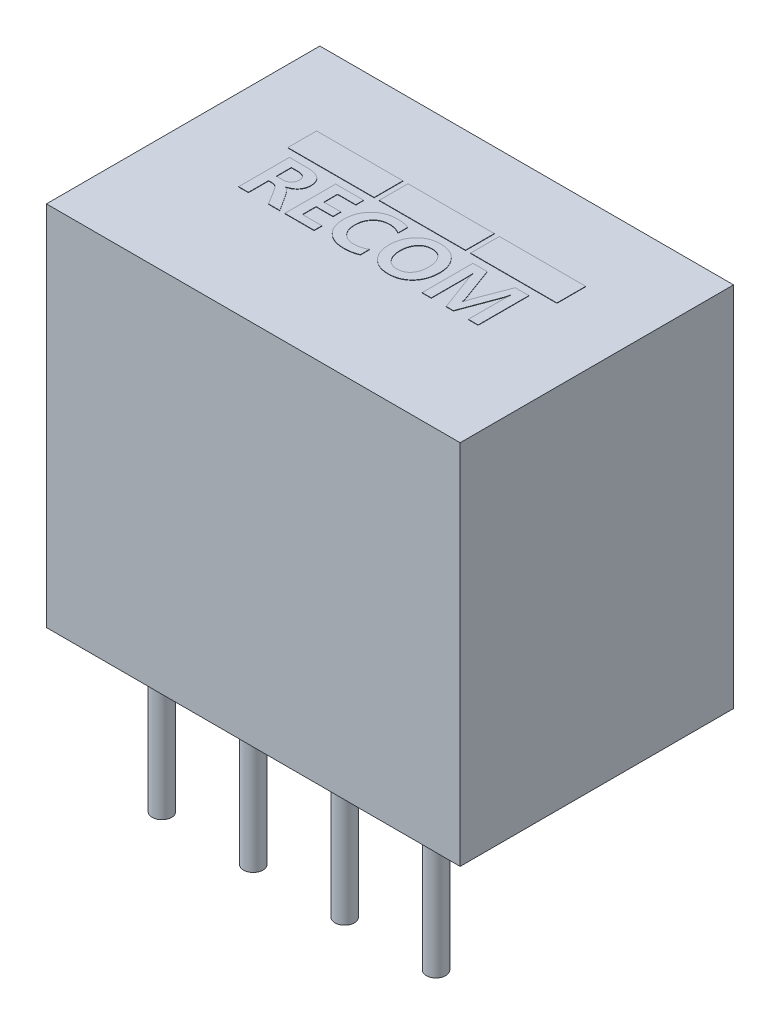
SolidWorks part; units mm, degrees
ref_plane "Front Plane" through (0, 0, 0) normal (0, 0, 1) x (1, 0, 0)
ref_plane "Top Plane" through (0, 0, 0) normal (0, 1, 0) x (1, 0, 0)
ref_plane "Right Plane" through (0, 0, 0) normal (1, 0, 0) x (0, 0, -1)
sketch "Sketch1" plane through (0, 0, 0) normal (0, 1, 0) x (1, 0, 0)
  line L0 (1.27, -1.2182) -> (1.27, -50000.2308) construction
  line L1 (-5.75, -3.8) -> (5.75, -3.8)
  line L2 (-5.75, -3.8) -> (-5.75, 3.8)
  line L3 (-5.75, 3.8) -> (5.75, 3.8)
  line L4 (5.75, -3.8) -> (5.75, 3.8)
  line L5 (-5.75, -3.8) -> (5.75, 3.8) construction
  line L6 (-5.75, 3.8) -> (5.75, -3.8) construction
  line L7 (-3.81, 1.0683) -> (-3.81, -49998.9317) construction
  line L8 (-1.27, -9.2663) -> (-1.27, 2.0854) construction
  line L9 (3.81, -9.3297) -> (3.81, -3.2594) construction
  line L10 (0, 0) -> (0, -6.7717) construction
  circle A0 centre (-1.27, -2.53) radius 0.27
  circle A1 centre (-3.81, -2.53) radius 0.27
  circle A2 centre (1.27, -2.53) radius 0.27
  circle A3 centre (3.81, -2.53) radius 0.27
  point P0 (0, 0)
  dimension "D3" = 0.54
  dimension "D1" = 11.5
  dimension "D2" = 7.6
  dimension "D4" = 1.27
  dimension "D5" = 2.54
  dimension "D6" = 2.54
  dimension "D7" = 2.54
  dimension "D8" = 1.27
extrude "Boss-Extrude1" add sketch "Sketch1" along normal blind 10.2 contours L1 L4 L3 L2 A2 A1 A0 | A0 | A2 | A1 | A3 region at (0, 0, -0.0268) region at (-1.27, 0, 2.53) region at (-3.81, 0, 2.53) region at (1.27, 0, 2.53) region at (3.81, 0, 2.53)
extrude "Boss-Extrude2" add sketch "Sketch1<3>" against normal blind 4.1 contours A2 | A0 | A1 | A3 region at (-1.27, 0, 2.53) region at (-3.81, 0, 2.53) region at (1.27, 0, 2.53)
sketch "Sketch1<3>" plane through (0, 0, 0) normal (0, 1, 0) x (1, 0, 0) same geometry as "Sketch1"
sketch "Sketch2" plane through (0, 10.2, 0) normal (0, 1, 0) x (1, 0, 0)
  line L0 (0, 7.4991) -> (0, -7.0772) construction
  line L1 (-3.74, 1.7) -> (-1.34, 1.7)
  line L2 (-3.74, 1.7) -> (-3.74, 0.9)
  line L3 (-3.74, 0.9) -> (-1.34, 0.9)
  line L4 (-1.34, 1.7) -> (-1.34, 0.9)
  line L5 (-3.74, 1.7) -> (-1.34, 0.9) construction
  line L6 (-3.74, 0.9) -> (-1.34, 1.7) construction
  line L7 (-1.2, 1.7) -> (1.2, 1.7)
  line L8 (-1.2, 1.7) -> (-1.2, 0.9)
  line L9 (-1.2, 0.9) -> (1.2, 0.9)
  line L10 (1.2, 1.7) -> (1.2, 0.9)
  line L11 (-1.2, 1.7) -> (1.2, 0.9) construction
  line L12 (-1.2, 0.9) -> (1.2, 1.7) construction
  line L13 (1.34, 1.7) -> (3.74, 1.7)
  line L14 (1.34, 1.7) -> (1.34, 0.9)
  line L15 (1.34, 0.9) -> (3.74, 0.9)
  line L16 (3.74, 1.7) -> (3.74, 0.9)
  line L17 (1.34, 1.7) -> (3.74, 0.9) construction
  line L18 (1.34, 0.9) -> (3.74, 1.7) construction
  line L19 (-2.54, 5.6376) -> (-2.54, 4.8793) construction
  line L20 (2.54, 7.0888) -> (2.54, -8.1777) construction
  line L21 (-5.75, -3.8) -> (5.75, -3.8) construction
  line L22 (-5.75, 3.8) -> (5.75, 3.8) construction
  text T0 "RECOM" font "@Malgun Gothic" height in points 5
  point P1 (-2.54, 1.3)
  point P6 (0, 1.3)
  point P11 (2.54, 1.3)
  point P24 (0, -3.8)
  point P25 (0, 0)
  point P26 (0, 0)
  point P27 (0, 0)
  point P30 (1.6332, 2.15)
  point P31 (0, 0)
  dimension "D1" = 2.54
  dimension "D2" = 2.54
  dimension "D3" = 0.8
  dimension "D4" = 2.5
  dimension "D5" = 2.4
extrude "Boss-Extrude3" add sketch "Sketch2" along normal blind 0.01
